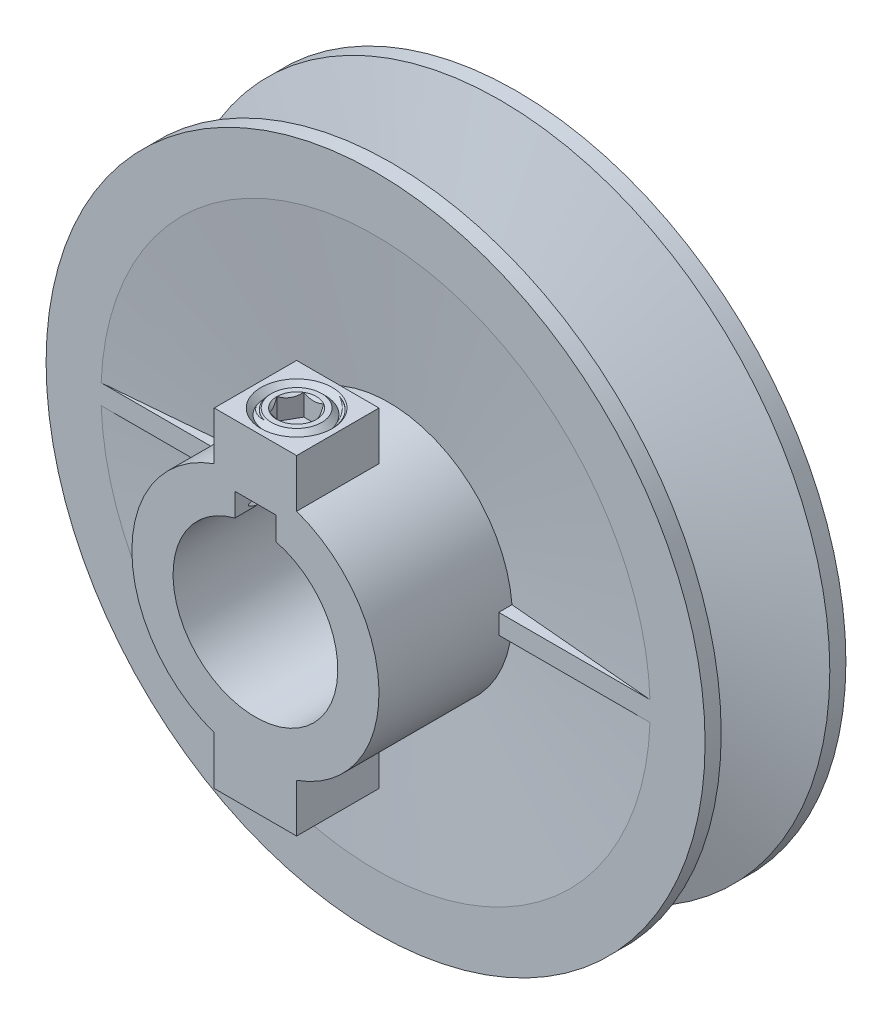
SolidWorks part; units mm, degrees
ref_plane "Front Plane" through (0, 0, 0) normal (0, 0, 1) x (1, 0, 0)
ref_plane "Top Plane" through (0, 0, 0) normal (0, 1, 0) x (1, 0, 0)
ref_plane "Right Plane" through (0, 0, 0) normal (1, 0, 0) x (0, 0, -1)
sketch "Sketch1" plane through (0, 0, 0) normal (1, 0, 0) x (0, 0, -1)
  line L0 (-22.0345, 0) -> (8.1407, 0) construction
  line L1 (-6.2793, 38.1) -> (6.2793, 38.1) construction
  line L2 (6.2793, 38.1) -> (8.1407, 38.1)
  line L5 (-8.1407, 38.1) -> (6.2793, 38.1) construction
  line L7 (-22.0345, 14.2875) -> (-22.0345, -14.2875) construction
  line L10 (-8.1407, 31.75) -> (-6.6129, 14.2875)
  line L13 (-6.2793, 38.1) -> (-2.3965, 25.4)
  line L14 (-2.3965, 25.4) -> (2.3965, 25.4)
  line L15 (2.3965, 25.4) -> (6.2793, 38.1)
  line L16 (8.1407, 9.525) -> (-22.0345, 9.525) construction
  line L17 (0, 38.1) -> (0, 0) construction
  line L18 (-6.2793, 38.1) -> (-8.1407, 38.1)
  line L20 (-22.0345, 0) -> (-22.0345, 9.525) construction
  line L22 (5.3086, 34.925) -> (-5.3086, 34.925) construction
  line L23 (8.1407, 38.1) -> (8.1407, 0) construction
  line L24 (8.1407, 31.75) -> (6.6129, 14.2875)
  line L26 (-22.0345, 14.2875) -> (-7.747, 14.2875)
  line L27 (-7.747, 14.2875) -> (8.1407, 14.2875) construction
  line L28 (-8.1407, 34.925) -> (-5.3086, 34.925) construction
  line L31 (-22.0345, 14.2875) -> (-22.0345, 0)
  line L32 (-8.1407, 31.75) -> (-8.1407, 38.1)
  line L33 (8.1407, 38.1) -> (8.1407, 31.75)
  line L34 (-22.0345, 0) -> (8.1407, 0)
  line L35 (8.1407, 0) -> (8.1407, 14.2875)
  line L37 (-6.6129, 14.2875) -> (6.6129, 14.2875) construction
  line L39 (-7.747, 14.2875) -> (-6.6129, 14.2875)
  line L40 (8.1407, 14.2875) -> (6.6129, 14.2875)
  line L42 (-7.747, 14.2875) -> (-7.747, 0) construction
  point P6 (0, 14.2875)
  point P16 (0, 25.4)
  point P25 (-7.747, 0)
  dimension "D1" = 5
revolve "Revolve1" add sketch "Sketch1" angle 360 about L0
sketch "Sketch2" plane through (0, 0, 0) normal (0, 1, 0) x (0, 0, -1)
  line L0 (-6.2793, 38.1) -> (-8.1407, 38.1) construction
  line L1 (-8.1407, 38.1) -> (-8.1407, -38.1) construction
  line L4 (-6.5907, 14.0335) -> (-8.1407, 31.75)
  line L5 (-6.6129, 14.2875) -> (-22.0345, 14.2875) construction
  line L6 (-8.1407, 14.0335) -> (-6.5907, 14.0335)
  line L7 (-8.1407, 14.0335) -> (-8.1407, 31.75)
  line L8 (-6.6129, 14.2875) -> (-8.1407, 31.75) construction
  line L11 (8.1407, 14.0335) -> (6.5907, 14.0335)
  line L12 (6.5907, 14.0335) -> (8.1407, 31.75)
  line L13 (0, 0) -> (0, 38.1) construction
  line L14 (8.1407, 14.0335) -> (8.1407, 31.75)
  dimension "D1" = 0.254
extrude "Boss-Extrude1" add sketch "Sketch2" along normal mid plane 2.286
pattern_circular "CirPattern1" count 2 over 360 of "Boss-Extrude1"
sketch "Sketch3" plane through (0, 0, -8.1407) normal (0, 0, -1) x (-1, 0, 0)
  circle A0 centre (0, 0) radius 9.525
  circle A1 centre (0, 0) radius 34.925 construction
  point P4 (0, 9.525)
extrude "Cut-Extrude1" cut sketch "Sketch3" against normal up to vertex (30.1752 mm away) up to point (0, 0, 22.0345)
sketch "Sketch4" plane through (0, 0, -8.1407) normal (0, 0, -1) x (-1, 0, 0)
  line L0 (2.3812, 9.525) -> (-2.3812, 9.525) construction
  line L1 (2.3813, 11.9062) -> (-2.3813, 11.9062)
  line L2 (2.3813, 11.9062) -> (2.3812, 7.1437)
  line L3 (2.3812, 7.1437) -> (-2.3812, 7.1437)
  line L4 (-2.3813, 11.9062) -> (-2.3812, 7.1437)
  dimension "Keyway Wd." = 4.7625
  dimension "Keyway Dp." = 2.3813
extrude "Cut-Extrude2" cut sketch "Sketch4" against normal up to vertex (30.1752 mm away) up to point (0, 0, 22.0345)
ref_plane "Plane1" through (0, 14.2875, 0) normal (0, 1, 0) x (-1, 0, 0)
sketch "Sketch5" plane through (0, 14.2875, 0) normal (0, 1, 0) x (-1, 0, 0)
  line L0 (0, 22.0345) -> (0, 0) construction
  line L1 (4.7625, 12.5095) -> (-4.7625, 12.5095)
  line L2 (4.7625, 12.5095) -> (4.7625, 22.0345)
  line L3 (4.7625, 22.0345) -> (-4.7625, 22.0345)
  line L4 (-4.7625, 12.5095) -> (-4.7625, 22.0345)
  line L5 (14.2875, 22.0345) -> (-14.2875, 22.0345) construction
  dimension "D1" = 9.525
extrude "Boss-Extrude2" add sketch "Sketch5" against normal up to surface (5.5796 mm away) from offset 4.7625 up to face at (14.2875, 0, 22.0345)
mirror "Mirror1" about plane through (0, 0, 0) normal (0, 1, 0) of "Boss-Extrude2"
sketch "Sketch6" plane through (0, 19.05, 0) normal (0, 1, 0) x (-1, 0, 0)
  line L0 (0, 12.5095) -> (0, 22.0345) construction
  line L1 (4.7625, 22.0345) -> (-4.7625, 22.0345) construction
  line L2 (-4.7625, 12.5095) -> (4.7625, 12.5095) construction
  line L7 (0, 21.2407) -> (0, 19.8296) construction
  circle A0 centre (0, 17.272) radius 3.9688 construction
  circle A1 centre (0, 17.272) radius 3.0868
  dimension "D3" = 0.8819
extrude "Cut-Extrude3" cut sketch "Sketch6" against normal up to vertex (19.05 mm away) up to point (0, 0, 22.0345)
sketch "Sketch7" plane through (0, 19.05, 0) normal (0, 1, 0) x (-1, 0, 0)
  circle A0 centre (0, 17.272) radius 3.9688 construction
  circle A1 centre (0, 17.272) radius 3.9688
  point P3 (0, 21.2407)
curve "Helix/Spiral1" pitch 1.4111 height 15.6986 radius 3.9688 centre (0, 19.05, 17.272) axis (0, -1, 0) start towards (0, 0, 1)
sketch "Sketch8" plane through (0, 0, 0) normal (1, 0, 0) x (0, 0, -1)
  line L0 (-20.1714, 20.4611) -> (-20.1714, 19.05) construction
  line L1 (-20.1714, 19.05) -> (-21.3935, 19.7556) construction
  line L2 (-21.3935, 19.7556) -> (-20.1714, 20.4611) construction
  line L3 (-20.1714, 19.05) -> (-21.2407, 19.05) construction
  line L4 (-21.2407, 19.05) -> (-21.2407, 19.6674) construction
  line L5 (-21.2407, 19.6674) -> (-21.2407, 19.8438) construction
  line L6 (-20.3242, 19.1382) -> (-20.3242, 20.3729) construction
  line L7 (-21.3935, 19.7556) -> (-21.2407, 19.7556) construction
  line L8 (-20.3242, 19.7556) -> (-20.1714, 19.7556) construction
  line L9 (-20.2478, 20.417) -> (-20.2478, 19.0941)
  line L10 (-20.2478, 19.0941) -> (-21.2407, 19.6674)
  line L11 (-21.2407, 19.6674) -> (-21.2407, 19.8438)
  line L12 (-21.2407, 19.8438) -> (-20.2478, 20.417)
  point P16 (-20.2478, 19.7556)
  dimension "D1" = 1.4111
  dimension "D2" = 0.1764
sweep "Cut-Sweep1" cut profiles "Sketch8" path "Helix/Spiral1" align with end faces yes
sketch "Sketch9" plane through (0, 19.05, 0) normal (0, 1, 0) x (-1, 0, 0)
  circle A0 centre (0, 17.272) radius 4.1215
extrude "Cut-Extrude4" cut sketch "Sketch9" against normal through all draft 45
sketch "Sketch10" plane through (0, 0, 0) normal (1, 0, 0) x (0, 0, -1)
  line L0 (-17.272, 19.05) -> (-17.272, 11.1125) construction
  line L1 (-21.2407, 12.1818) -> (-21.2407, 17.9807)
  line L2 (-17.272, 19.05) -> (-21.2407, 19.05) construction
  line L3 (-17.272, 19.05) -> (-17.272, 11.1125)
  line L4 (-17.272, 11.1125) -> (-21.2407, 11.1125) construction
  line L5 (-21.2407, 19.05) -> (-21.2407, 11.1125) construction
  line L6 (-20.1714, 19.05) -> (-21.2407, 17.9807)
  line L7 (-21.2407, 12.1818) -> (-20.1714, 11.1125)
  line L8 (-20.1714, 19.05) -> (-17.272, 19.05)
  line L9 (-20.1714, 11.1125) -> (-17.272, 11.1125)
  line L10 (-12.5095, 19.05) -> (-22.0345, 19.05) construction
  line L11 (-20.1714, 19.05) -> (-21.2407, 19.05) construction
  line L12 (-21.2407, 19.05) -> (-21.2407, 17.9807) construction
revolve "Revolve3" add sketch "Sketch10" angle 360 about L0
sketch "Sketch11" plane through (0, 19.05, 0) normal (0, 1, 0) x (-1, 0, 0)
  circle A1 centre (0, 17.272) radius 3.9688
  circle A2 centre (0, 17.272) radius 3.9688
  dimension "D1" = 0
curve "Helix/Spiral2" pitch 1.4111 height 9.3486 turns 6.625
sketch "Sketch12" plane through (0, 0, 0) normal (1, 0, 0) x (0, 0, -1)
  line L0 (-21.3171, 19.7115) -> (-21.3171, 18.3885)
  line L1 (-21.3171, 19.7556) -> (-21.3171, 19.7115) construction
  line L2 (-21.3935, 19.7556) -> (-21.2407, 19.7556) construction
  line L3 (-20.1714, 19.05) -> (-21.3935, 19.7556) construction
  line L4 (-21.3171, 19.7115) -> (-20.3242, 19.1382)
  line L5 (-20.3242, 19.1382) -> (-20.3242, 18.9618)
  line L6 (-20.3242, 18.9618) -> (-21.3171, 18.3885)
  line L7 (-21.3935, 19.7556) -> (-20.1714, 19.05) construction
  line L8 (-20.1714, 19.05) -> (-21.3935, 18.3444) construction
  line L9 (-21.3935, 18.3444) -> (-21.3935, 19.7556) construction
sweep "Cut-Sweep2" cut profiles "Sketch12" path "Helix/Spiral2" align with end faces yes
sketch "Sketch13" plane through (0, 19.05, 0) normal (0, 1, 0) x (1, 0, 0)
  line L1 (2.2914, -17.272) -> (1.1457, -15.2876)
  line L2 (1.1457, -15.2876) -> (-1.1457, -15.2876)
  line L3 (-1.1457, -15.2876) -> (-2.2914, -17.272)
  line L4 (-2.2914, -17.272) -> (-1.1457, -19.2564)
  line L5 (-1.1457, -19.2564) -> (1.1457, -19.2564)
  line L6 (1.1457, -19.2564) -> (2.2914, -17.272)
  circle A0 centre (0, -17.272) radius 1.9844 construction
  dimension "D1" = 3.9688
extrude "Cut-Extrude5" cut sketch "Sketch13" against normal blind 2.4805
sketch "Sketch14" plane through (0, 19.05, 0) normal (0, 1, 0) x (1, 0, 0)
  circle A0 centre (0, -17.272) radius 2.2914
extrude "Cut-Extrude6" cut sketch "Sketch14" against normal through all draft 45
equation "\"D3@Sketch6\" = \"Screw Pitch@Sketch6\" * 5 / 8"
equation "\"D4@Helix/Spiral1\" = \"Screw Pitch@Sketch6\""
equation "\"D3@Helix/Spiral1\" = \"D4@Helix/Spiral1\" + ( \"Hub Dia.@Sketch1\" / 2 ) "
equation "\"D1@Sketch8\" = \"D4@Helix/Spiral1\""
equation "\"D2@Sketch8\" = \"D1@Sketch8\" / 8"
equation "\"D4@Helix/Spiral2\" = \"D4@Helix/Spiral1\""
equation "\"D3@Helix/Spiral2\" = \"D4@Helix/Spiral2\" + \"Screw Length@Sketch10\""
equation "\"D1@Sketch13\" = \"Screw OD@Sketch6\" / 2"
equation "\"D1@Cut-Extrude5\" = \"D1@Sketch13\" * 5 / 8"
